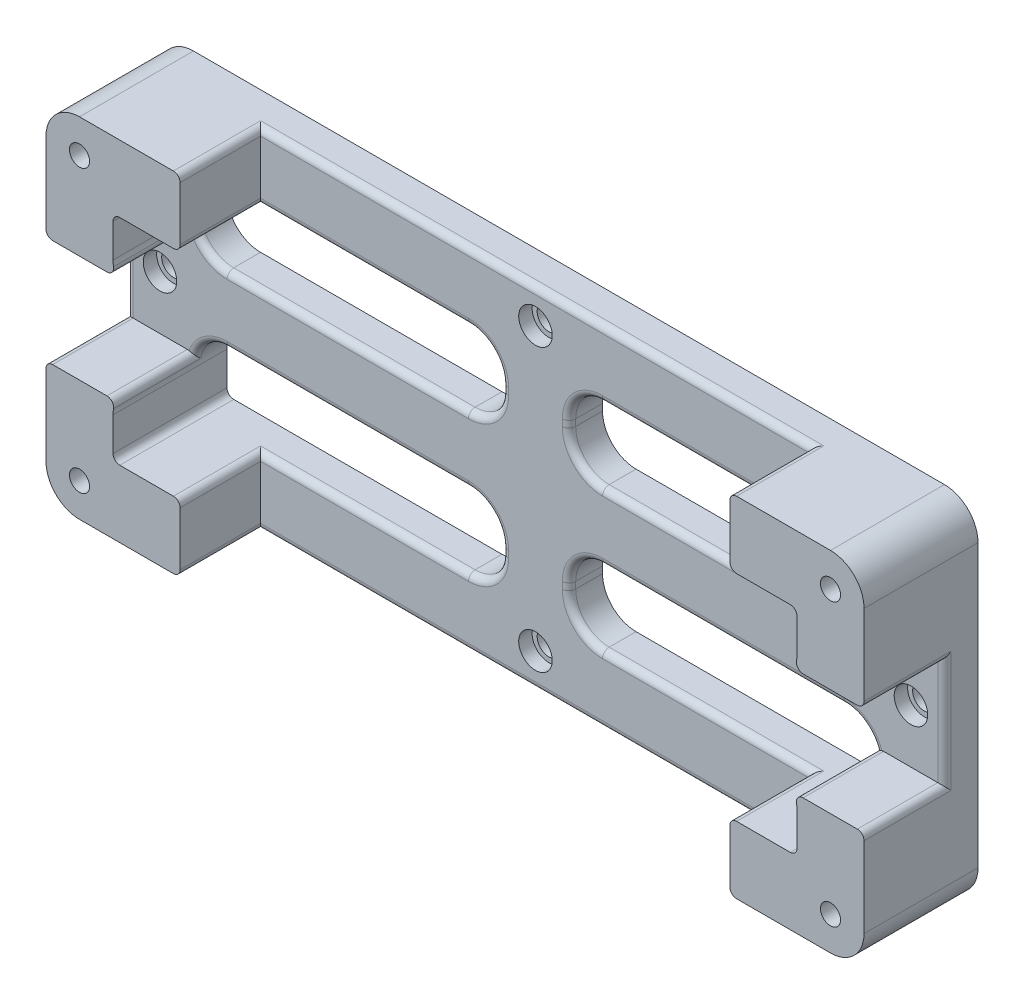
SolidWorks part; units mm, degrees
ref_plane "Front Plane" through (0, 0, 0) normal (0, 0, 1) x (1, 0, 0)
ref_plane "Top Plane" through (0, 0, 0) normal (0, 1, 0) x (1, 0, 0)
ref_plane "Right Plane" through (0, 0, 0) normal (1, 0, 0) x (0, 0, -1)
sketch "Sketch1" plane through (0, 0, 0) normal (0, 0, 1) x (1, 0, 0)
  line L0 (0, 0) -> (102, 0)
  line L1 (102, 0) -> (102, 32)
  line L2 (102, 32) -> (0, 32)
  line L3 (0, 32) -> (0, 0)
  line L4 (-10, -10) -> (112, -10)
  line L5 (112, -10) -> (112, 42)
  line L6 (112, 42) -> (-10, 42)
  line L7 (-10, 42) -> (-10, -10)
  dimension "D1" = 102
  dimension "D2" = 32
  dimension "D3" = 10
  dimension "D4" = 10
  dimension "D5" = 10
  dimension "D6" = 10
extrude "Boss-Extrude1" add sketch "Sketch1" along normal blind 5
sketch "Sketch2" plane through (0, 0, 5) normal (0, 0, 1) x (1, 0, 0)
  line L0 (51, 32) -> (56, 32)
  line L2 (102, 32) -> (0, 32) construction
  line L3 (51, 32) -> (46, 32)
  line L4 (0, 16) -> (0, 21)
  line L5 (0, 32) -> (0, 0) construction
  line L6 (0, 16) -> (0, 11)
  line L7 (51, 0) -> (56, 0)
  line L8 (0, 0) -> (102, 0) construction
  line L9 (51, 0) -> (46, 0)
  line L10 (102, 16) -> (102, 21)
  line L11 (102, 0) -> (102, 32) construction
  line L12 (102, 16) -> (102, 11)
  line L13 (46, 0) -> (46, 11)
  line L14 (46, 11) -> (0, 11)
  line L15 (0, 21) -> (46, 21)
  line L16 (46, 21) -> (46, 32)
  line L17 (56, 32) -> (56, 21)
  line L18 (56, 21) -> (102, 21)
  line L19 (102, 11) -> (56, 11)
  line L20 (56, 11) -> (56, 0)
  dimension "D1" = 5
  dimension "D2" = 5
  dimension "D3" = 5
  dimension "D4" = 5
  dimension "D5" = 5
  dimension "D6" = 5
  dimension "D7" = 5
  dimension "D8" = 5
extrude "Boss-Extrude2" add sketch "Sketch2" against normal blind 5
sketch "Sketch3" plane through (0, 0, 5) normal (0, 0, 1) x (1, 0, 0)
  line L0 (-10, 42) -> (10, 42)
  line L1 (112, 42) -> (-10, 42) construction
  line L2 (10, 42) -> (10, 32)
  line L3 (46, 32) -> (0, 32) construction
  line L4 (10, 32) -> (0, 32)
  line L5 (0, 32) -> (0, 24)
  line L6 (0, 32) -> (0, 21) construction
  line L7 (0, 24) -> (-10, 24)
  line L8 (-10, 42) -> (-10, -10) construction
  line L9 (-10, 24) -> (-10, 42)
  line L10 (-10, -10) -> (10, -10)
  line L11 (-10, -10) -> (112, -10) construction
  line L12 (10, -10) -> (10, 0)
  line L13 (0, 0) -> (46, 0) construction
  line L14 (10, 0) -> (0, 0)
  line L15 (0, 0) -> (0, 8)
  line L16 (0, 11) -> (0, 0) construction
  line L17 (0, 8) -> (-10, 8)
  line L18 (-10, 8) -> (-10, -10)
  line L19 (112, -10) -> (112, 8)
  line L20 (112, -10) -> (112, 42) construction
  line L21 (112, 8) -> (102, 8)
  line L22 (102, 0) -> (102, 11) construction
  line L23 (102, 8) -> (102, 0)
  line L24 (102, 0) -> (92, 0)
  line L25 (56, 0) -> (102, 0) construction
  line L26 (92, 0) -> (92, -10)
  line L27 (92, -10) -> (112, -10)
  line L28 (112, 42) -> (92, 42)
  line L31 (102, 32) -> (102, 24)
  line L32 (102, 21) -> (102, 32) construction
  line L33 (102, 24) -> (112, 24)
  line L34 (112, 24) -> (112, 42)
  line L35 (102, 32) -> (92, 32)
  line L36 (102, 32) -> (56, 32) construction
  line L37 (92, 32) -> (92, 42)
  dimension "D1" = 20
  dimension "D2" = 18
  dimension "D3" = 20
  dimension "D4" = 18
  dimension "D5" = 18
  dimension "D6" = 20
  dimension "D7" = 20
  dimension "D8" = 18
extrude "Boss-Extrude3" add sketch "Sketch3" along normal blind 12
sketch "Sketch4" plane through (0, 0, 17) normal (0, 0, 1) x (1, 0, 0)
  line L0 (112, -10) -> (112, 8) construction
  line L1 (92, -10) -> (112, -10) construction
  line L2 (112, 24) -> (112, 42) construction
  line L3 (112, 42) -> (92, 42) construction
  line L4 (-10, -10) -> (10, -10) construction
  line L5 (-10, 8) -> (-10, -10) construction
  line L6 (10, 42) -> (-10, 42) construction
  line L7 (-10, 42) -> (-10, 24) construction
  circle A0 centre (-5, 37) radius 1.5
  circle A1 centre (107, 37) radius 1.5
  circle A2 centre (107, -5) radius 1.5
  circle A3 centre (-5, -5) radius 1.5
  dimension "D1" = 3
  dimension "D2" = 3
  dimension "D3" = 3
  dimension "D4" = 3
  dimension "D5" = 5
  dimension "D6" = 5
  dimension "D7" = 5
  dimension "D8" = 5
  dimension "D9" = 5
  dimension "D10" = 5
  dimension "D11" = 5
  dimension "D12" = 5
extrude "Cut-Extrude1" cut sketch "Sketch4" against normal blind 7
sketch "Sketch5" plane through (0, 0, 5) normal (0, 0, 1) x (1, 0, 0)
  line L0 (46, 21) -> (0, 21) construction
  line L1 (46, 32) -> (46, 21) construction
  line L2 (102, 21) -> (56, 21) construction
  line L3 (46, 11) -> (46, 0) construction
  line L4 (-10, 24) -> (-10, 8) construction
  line L5 (112, 8) -> (112, 24) construction
  line L6 (10, -10) -> (92, -10) construction
  line L7 (92, 42) -> (10, 42) construction
  circle A0 centre (-5, 16) radius 1.75
  circle A1 centre (51, 37) radius 1.75
  circle A2 centre (107, 16) radius 1.75
  circle A3 centre (51, -5) radius 1.75
  dimension "D1" = 3.5
  dimension "D2" = 3.5
  dimension "D3" = 3.5
  dimension "D4" = 3.5
  dimension "D5" = 5
  dimension "D6" = 5
  dimension "D7" = 5
  dimension "D8" = 5
  dimension "D9" = 5
  dimension "D10" = 5
  dimension "D11" = 5
  dimension "D12" = 5
extrude "Cut-Extrude2" cut sketch "Sketch5" against normal through all
sketch "Sketch6" plane through (0, 0, 5) normal (0, 0, 1) x (1, 0, 0)
  circle A0 centre (-5, 16) radius 2.5
  circle A1 centre (51, 37) radius 2.5
  circle A2 centre (51, -5) radius 2.5
  circle A3 centre (107, 16) radius 2.5
  dimension "D1" = 5
  dimension "D2" = 5
  dimension "D3" = 5
  dimension "D4" = 5
extrude "Cut-Extrude3" cut sketch "Sketch6" against normal blind 2
fillet "Fillet1" radius 5 16 edges at (-10, 42, 8.5) (112, 42, 8.5) (112, -10, 8.5) (-10, -10, 8.5) (56, 11, 2.5) (56, 0, 2.5) (56, 21, 2.5) (102, 21, 2.5) (56, 32, 2.5) (102, 11, 2.5) (46, 0, 2.5) (46, 11, 2.5) (0, 11, 2.5) (0, 21, 2.5) (46, 32, 2.5) (46, 21, 2.5)
fillet "Fillet2" radius 1 48 edges at (76.5, 0, 5) (57.4645, 1.4645, 5) (99.7386, 10.1833, 5) (79, 11, 5) (57.4645, 9.5355, 5) (2.2614, 10.1833, 5) (23, 11, 5) (44.5355, 9.5355, 5) (25.5, 0, 5) (44.5355, 1.4645, 5) (99.7386, 21.8167, 5) (79, 21, 5) (57.4645, 22.4645, 5) (76.5, 32, 5) (57.4645, 30.5355, 5) (25.5, 32, 5) (44.5355, 30.5355, 5) (2.2614, 21.8167, 5) (23, 21, 5) (44.5355, 22.4645, 5) (92, 42, 11) (10, 32, 11) (10, 42, 11) (10, 0, 11) (10, -10, 11) (51, 42, 5) (51, -10, 5) (92, -10, 11) (92, 0, 11) (112, 8, 11) (112, 24, 11) (112, 16, 5) (56, 5.5, 5) (46, 5.5, 5) (56, 26.5, 5) (46, 26.5, 5) (92, 32, 11) (-10, 24, 11) (-10, 16, 5) (-10, 8, 11) (0, 0, 8.5) (102, 0, 8.5) (0, 32, 8.5) (102, 32, 8.5) (101.5826, 8, 11) (101.5826, 24, 11) (0.4174, 8, 11) (0.4174, 24, 11)
